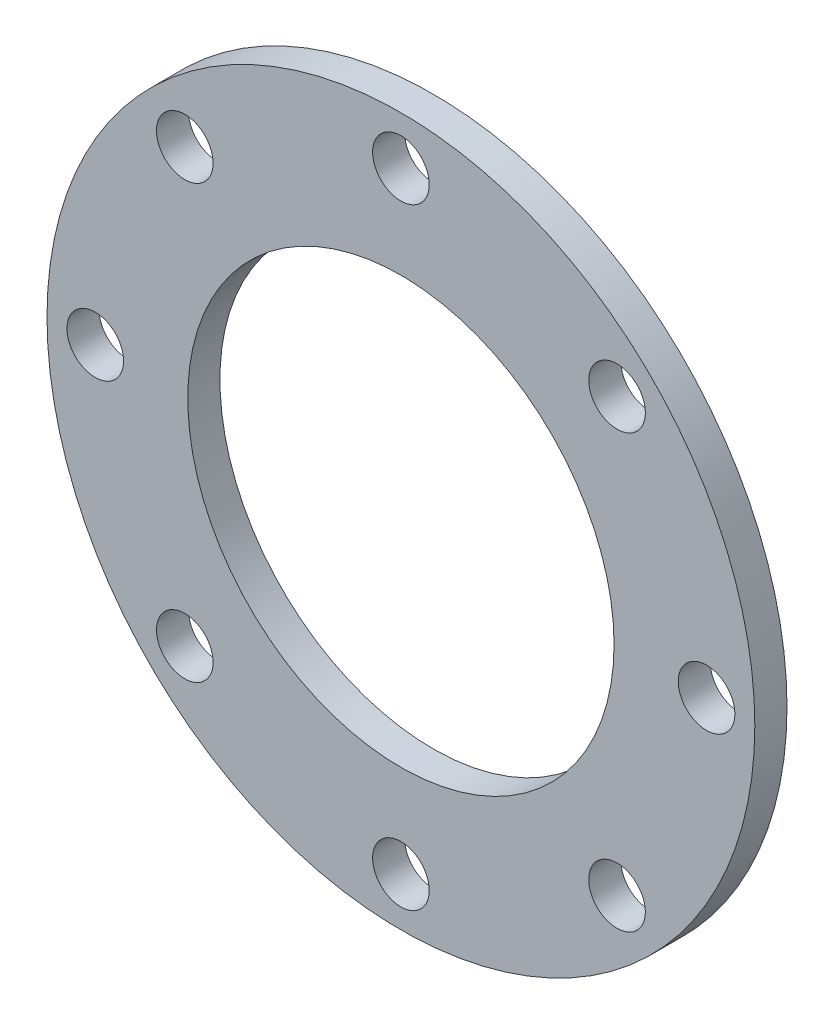
SolidWorks part; units mm, degrees
material "PE High Density"
ref_plane "Front Plane" through (0, 0, 0) normal (0, 0, 1) x (1, 0, 0)
ref_plane "Top Plane" through (0, 0, 0) normal (0, 1, 0) x (1, 0, 0)
ref_plane "Right Plane" through (0, 0, 0) normal (1, 0, 0) x (0, 0, -1)
sketch "Sketch1" plane through (0, 0, 0) normal (0, 0, 1) x (1, 0, 0)
  circle A0 centre (0, 0) radius 139.7
  circle A1 centre (0, 0) radius 120.65 construction
  circle A2 centre (0, 0) radius 84.1375
  circle A3 centre (0, 120.65) radius 11.176
  circle A4 centre (85.3124, 85.3124) radius 11.176
  circle A5 centre (120.65, 0) radius 11.176
  circle A6 centre (85.3124, -85.3124) radius 11.176
  circle A7 centre (0, -120.65) radius 11.176
  circle A8 centre (-85.3124, -85.3124) radius 11.176
  circle A9 centre (-120.65, 0) radius 11.176
  circle A10 centre (-85.3124, 85.3124) radius 11.176
  point P23 (0, 0)
  dimension "D1" = 279.4
  dimension "D2" = 241.3
  dimension "D3" = 168.275
  dimension "D4" = 22.352
  dimension "D5" = 8
extrude "Boss-Extrude1" add sketch "Sketch1" along normal blind 12.7
equation "\"ID\"= 6.62500000in"
equation "\"BC\"= 9.5in"
equation "\"OD\"= 11in"
equation "\"HD\"= 0.88in"
equation "\"T\"= 0.5in"
equation "\"D1@Sketch1\"=\"OD\""
equation "\"D2@Sketch1\"=\"BC\""
equation "\"D3@Sketch1\"=\"ID\""
equation "\"D4@Sketch1\"=\"HD\""
equation "\"D1@Boss-Extrude1\"=\"T\""
